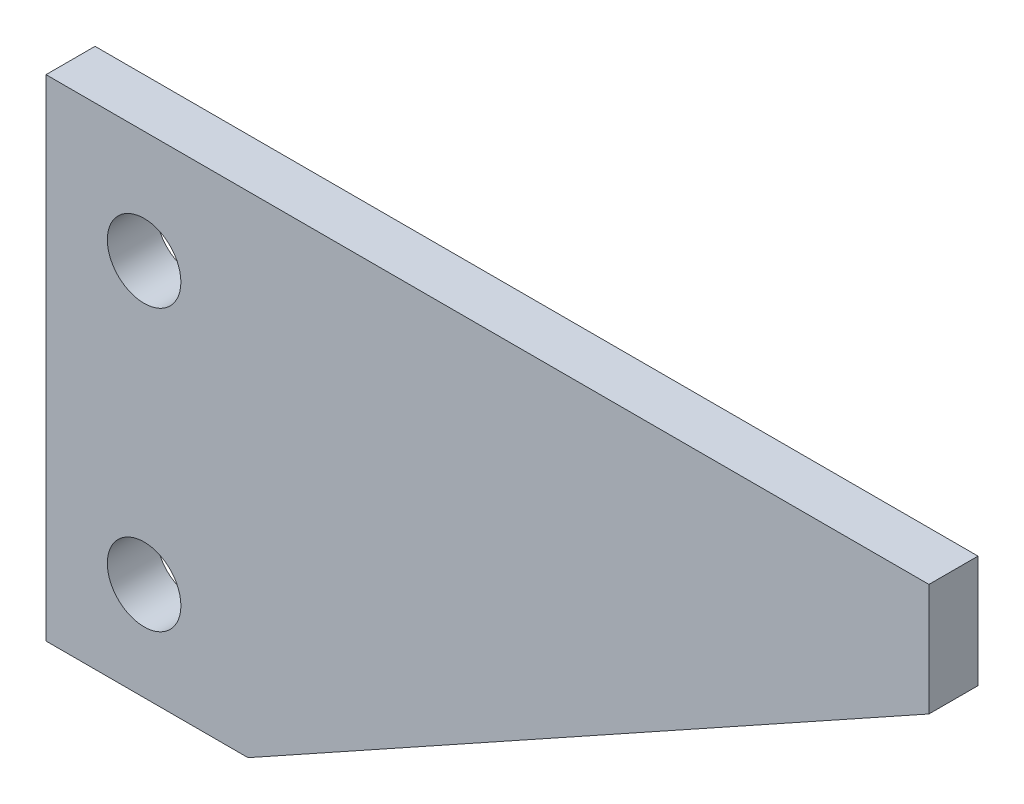
SolidWorks part; units mm, degrees
ref_plane "Front Plane" through (0, 0, 0) normal (0, 0, 1) x (1, 0, 0)
ref_plane "Top Plane" through (0, 0, 0) normal (0, 1, 0) x (1, 0, 0)
ref_plane "Right Plane" through (0, 0, 0) normal (1, 0, 0) x (0, 0, -1)
sketch "Sketch1" plane through (0, 0, 0) normal (0, 0, 1) x (1, 0, 0)
  line L0 (-49.1737, -50.1979) -> (43658.6902, 24231.9487) construction
  line L1 (-90, -50) -> (-48.8175, -50)
  line L2 (-90, -50) -> (-90, 50)
  line L3 (-90, 50) -> (90, 50)
  line L4 (90, 27.1208) -> (90, 50)
  line L7 (-48.8175, -50) -> (90, 27.1208)
  circle A0 centre (-70, 27.1208) radius 7.5
  circle A1 centre (-70, -30) radius 7.5
  point P0 (0, 0)
  point P4 (0, 50)
  point P10 (-90, 0)
  dimension "D6" = 15
  dimension "D7" = 15
  dimension "D1" = 100
  dimension "D2" = 180
  dimension "D3" = 20
  dimension "D4" = 158.8015
  dimension "D5" = 20
  dimension "D8" = 20
extrude "Boss-Extrude1" add sketch "Sketch1" along normal blind 5 and the other way blind 5
